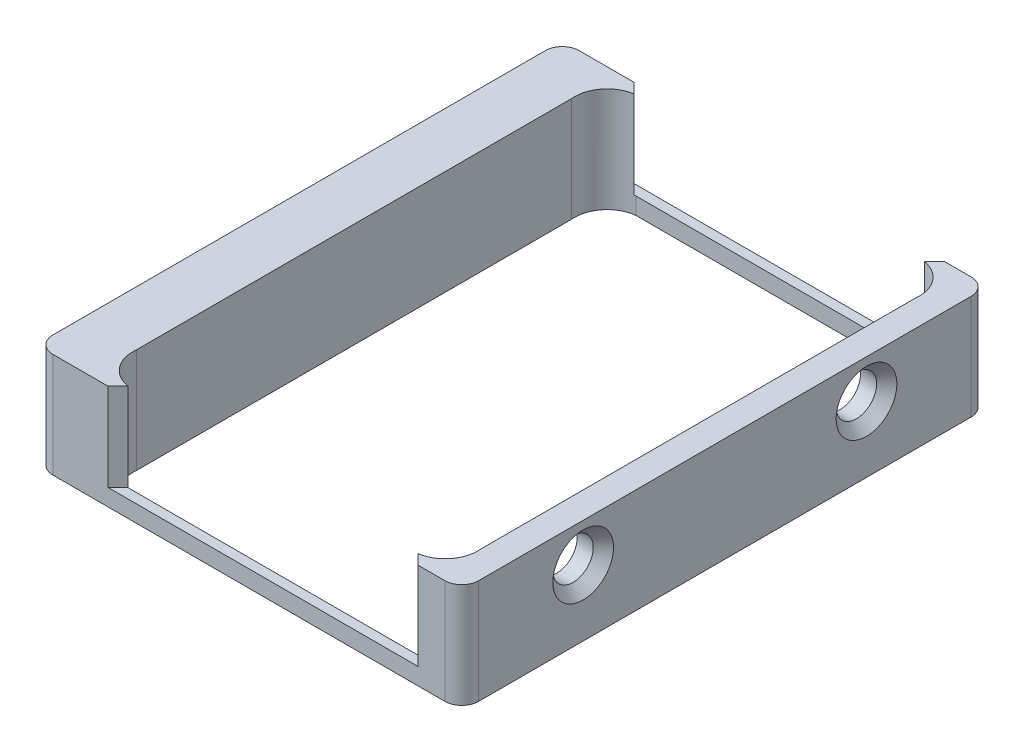
SolidWorks part; units mm, degrees
ref_plane "Front Plane" through (0, 0, 0) normal (0, 0, 1) x (1, 0, 0)
ref_plane "Top Plane" through (0, 0, 0) normal (0, 1, 0) x (1, 0, 0)
ref_plane "Right Plane" through (0, 0, 0) normal (1, 0, 0) x (0, 0, -1)
other "Configuration Table"
sketch "草图1" plane through (0, 0, 0) normal (0, 1, 0) x (1, 0, 0)
  line L0 (0, -75.1) -> (0, 75.1) construction
  line L1 (-51.1, 0) -> (51.1, 0) construction
  line L2 (-42.5, 75.1) -> (42.5, 75.1)
  line L3 (-51.1, -64.5) -> (-51.1, 64.5)
  line L4 (-42.5, -75.1) -> (42.5, -75.1)
  line L5 (51.1, -64.5) -> (51.1, 64.5)
  line L6 (-51.1, 0) -> (-67.3, 0) construction
  line L7 (-67.3, -78) -> (-67.3, 78)
  line L8 (51.1, 0) -> (58.9, 0) construction
  line L9 (58.9, -78) -> (58.9, 78)
  line L10 (-67.3, 78) -> (58.9, 78)
  line L11 (-67.3, -78) -> (58.9, -78)
  arc A4 (-51.1, 64.5) -> (-42.5, 75.1) centre (-41.5, 65.5) cw
  arc A5 (-51.1, -64.5) -> (-42.5, -75.1) centre (-41.5, -65.5) ccw
  arc A6 (42.5, -75.1) -> (51.1, -64.5) centre (41.5, -65.5) ccw
  arc A7 (42.5, 75.1) -> (51.1, 64.5) centre (41.5, 65.5) cw
  point P4 (0, 0)
  point P9 (0, 0)
  point P12 (0, 75.1)
  point P15 (-51.1, 0)
  point P27 (-67.3, 0)
  point P31 (58.9, 0)
  dimension "D1" = 16.2
  dimension "D4" = 85
  dimension "D2" = 51.1
  dimension "D3" = 7.8
  dimension "D5" = 129
extrude "凸台-拉伸1" add sketch "草图1" along normal blind 31
sketch "草图2" plane through (0, 31, 0) normal (0, 1, 0) x (1, 0, 0)
  line L0 (0, 0) -> (0, 78) construction
  line L1 (58.9, 78) -> (-67.3, 78) construction
  line L2 (-46, 78) -> (46, 78)
  line L3 (-43.1, 75.1) -> (43.1, 75.1)
  line L4 (-43.1, 75.1) -> (-42.7809, 74.7809)
  line L5 (42.5, 75.1) -> (-42.5, 75.1) construction
  line L6 (-43.1, 75.1) -> (-46, 78)
  line L7 (43.1, 75.1) -> (46, 78)
  line L8 (0, 0) -> (58.9, 0) construction
  line L9 (58.9, -78) -> (58.9, 78) construction
  line L14 (-42.7809, 74.7809) -> (-42.5, 75.1)
  line L15 (43.1, 75.1) -> (42.8724, 74.8724)
  line L16 (42.8724, 74.8724) -> (42.5, 75.1)
  line L17 (42.8724, -74.8724) -> (42.5, -75.1)
  line L18 (43.1, -75.1) -> (42.8724, -74.8724)
  line L19 (-42.7809, -74.7809) -> (-42.5, -75.1)
  line L20 (-43.1, -75.1) -> (-42.7809, -74.7809)
  line L21 (-43.1, -75.1) -> (43.1, -75.1)
  line L22 (-43.1, -75.1) -> (-46, -78)
  line L23 (-46, -78) -> (46, -78)
  line L24 (43.1, -75.1) -> (46, -78)
  point P8 (0, 78)
  point P14 (0, 75.1)
  line M6 (58.9, 78) -> (-67.3, 78)
  line M8 (-67.3, -78) -> (58.9, -78)
  line M10 (42.5, -75.1) -> (-42.5, -75.1)
  line M14 (-42.5, 75.1) -> (42.5, 75.1)
extrude "切除-拉伸1" cut sketch "草图2" against normal blind 26 contours L20 L19 | L20 L21 | L24 L21 L22 M10 M8 | L18 L17 | L21 L18 | L3 L7 L6 M6 M14 | L4 L14 | L3 L4 | L16 L15 | L15 L3 region at (0, 31, -76.5657) region at (-42.7936, 31, -74.9936) region at (42.8241, 31, -75.0241) region at (42.8241, 31, 75.0241) region at (0, 31, 76.5657) region at (-42.7936, 31, 74.9936)
fillet "圆角1" radius 5 4 edges at (-67.3, 15.5, -78) (58.9, 15.5, -78) (58.9, 15.5, 78) (-67.3, 15.5, 78)
sketch "草图5" plane through (58.9, 0, 0) normal (1, 0, 0) x (0, 0, -1)
  line L0 (-78, 0) -> (-78, 31) construction
  line L1 (-73, 0) -> (73, 0) construction
  line L2 (78, 31) -> (78, 0) construction
  point P0 (42, 19.55)
  point P2 (-42, 19.55)
  dimension "D1" = 36
  dimension "D2" = 19.55
  dimension "D3" = 36
  dimension "D4" = 19.55
hole_wizard "Ø12.0mm 暗销孔1" positions "草图5" profile "草图4" hole size "Ø12.0" standard "ANSI Metric"
sketch "草图4" plane through (58.9, 19.55, -42) normal (0, 1, 0) x (0, 0, -1)
  line L0 (0, 0) -> (0, 20.6052)
  line L1 (0, 20.6052) -> (6, 17)
  line L2 (6, 17) -> (6, 0)
  line L5 (6, 0) -> (0, 0)
  line L10 (0, 20.6052) -> (-6, 17) construction
  line L11 (0, -6.35) -> (0, 107.95) construction
  dimension "孔直径" = 12
  dimension "孔深度" = 17
  dimension "导头角度" = 118
sketch "草图6" plane through (-67.3, 0, 0) normal (-1, 0, 0) x (0, 0, 1)
  line L0 (0, 0) -> (0, 13.95) construction
  line L1 (0, 13.95) -> (-11, 13.95) construction
  circle A2 centre (-11, 13.95) radius 2.1
  circle A3 centre (11, 13.95) radius 2.1
  point P4 (0, 13.45)
  dimension "D1" = 4.2
extrude "切除-拉伸2" cut sketch "草图6" against normal blind 10
sketch "草图7" plane through (0, 0, 0) normal (0, -1, 0) x (1, 0, 0)
  circle A0 centre (-58.4934, 70.9643) radius 2.1
  circle A1 centre (53.705, 73.3482) radius 2.1
  circle A2 centre (-58.4934, -70.9643) radius 2.1
  circle A3 centre (53.705, -73.3482) radius 2.1
extrude "切除-拉伸3" cut sketch "草图7" against normal blind 10
chamfer "倒角1" distance 3 angle 45 2 edges at (58.9, 19.55, 36) (58.9, 19.55, -48)
